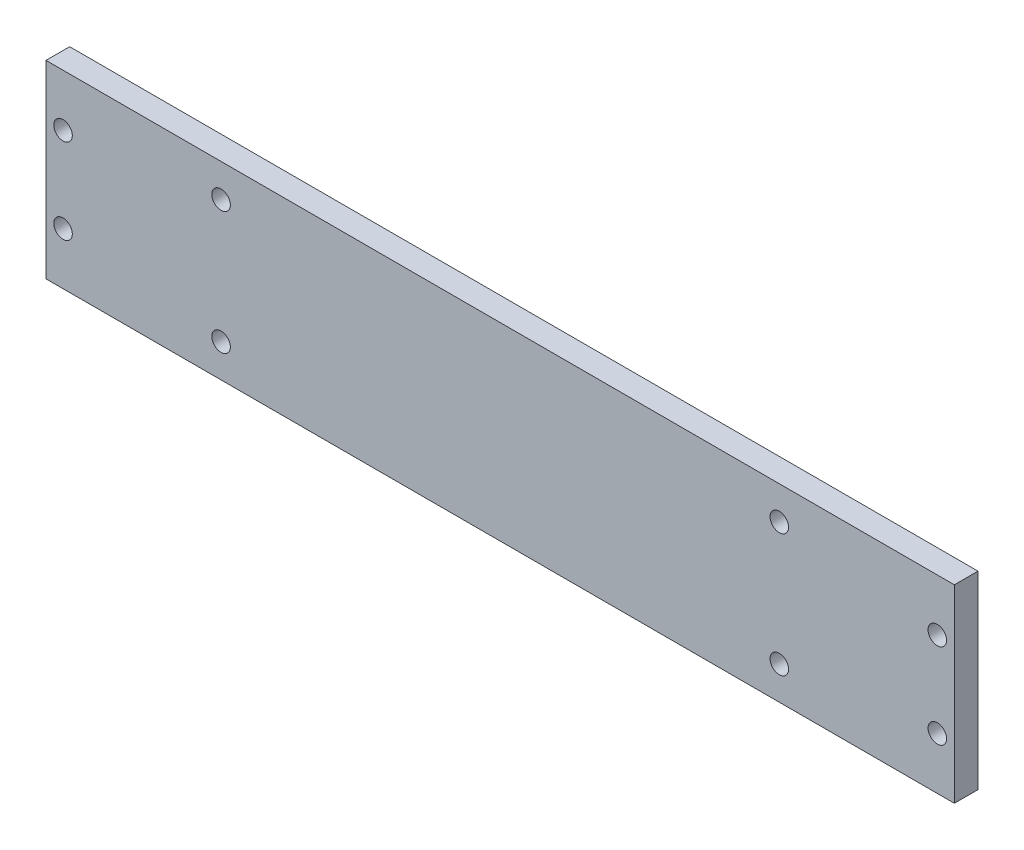
SolidWorks part; units mm, degrees
material "6061-T6 (SS)"
ref_plane "Front Plane" through (0, 0, 0) normal (0, 0, 1) x (1, 0, 0)
ref_plane "Top Plane" through (0, 0, 0) normal (0, 1, 0) x (1, 0, 0)
ref_plane "Right Plane" through (0, 0, 0) normal (1, 0, 0) x (0, 0, -1)
sketch "Sketch1" plane through (0, 0, 0) normal (0, 0, 1) x (1, 0, 0)
  line L1 (-121.92, 25.4) -> (121.92, 25.4)
  line L2 (-121.92, 25.4) -> (-121.92, -25.4)
  line L3 (-121.92, -25.4) -> (121.92, -25.4)
  line L4 (121.92, 25.4) -> (121.92, -25.4)
  line L5 (-121.92, 25.4) -> (121.92, -25.4) construction
  line L6 (-121.92, -25.4) -> (121.92, 25.4) construction
  point P0 (0, 0)
  dimension "D1" = 50.8
  dimension "D2" = 243.84
extrude "Boss-Extrude1" add sketch "Sketch1" along normal blind 6.35
sketch "Sketch2" plane through (0, 0, 6.35) normal (0, 0, 1) x (1, 0, 0)
  line L0 (121.92, -25.4) -> (121.92, 25.4) construction
  line L1 (-74.93, 16.51) -> (74.93, 16.51) construction
  line L2 (-74.93, 16.51) -> (-74.93, -16.51) construction
  line L3 (-74.93, -16.51) -> (74.93, -16.51) construction
  line L4 (74.93, 16.51) -> (74.93, -16.51) construction
  line L5 (-74.93, 16.51) -> (74.93, -16.51) construction
  line L6 (-74.93, -16.51) -> (74.93, 16.51) construction
  line L7 (117.348, -11.43) -> (-117.348, -11.43) construction
  line L8 (117.348, -11.43) -> (117.348, 11.43) construction
  line L9 (117.348, 11.43) -> (-117.348, 11.43) construction
  line L10 (-117.348, -11.43) -> (-117.348, 11.43) construction
  line L11 (117.348, -11.43) -> (-117.348, 11.43) construction
  line L12 (117.348, 11.43) -> (-117.348, -11.43) construction
  point P0 (0, 0)
  point P6 (0, 0)
  dimension "D1" = 149.86
  dimension "D2" = 33.02
  dimension "D3" = 4.572
  dimension "D4" = 22.86
hole_wizard "#10 Clearance Hole1" positions "Sketch3" profile "Sketch4" hole size "#10" standard "ANSI Inch" end condition through all
sketch "Sketch3" plane through (0, 0, 6.35) normal (0, 0, 1) x (1, 0, 0)
  point P0 (-74.93, 16.51)
  point P3 (-74.93, -16.51)
  point P6 (74.93, 16.51)
  point P9 (74.93, -16.51)
  point P12 (-117.348, 11.43)
  point P15 (-117.348, -11.43)
  point P18 (117.348, 11.43)
  point P21 (117.348, -11.43)
sketch "Sketch4" plane through (-74.93, 16.51, 6.35) normal (1, 0, 0) x (0, -1, 0)
  line L0 (0, 0) -> (0, 6.35)
  line L1 (0, 6.35) -> (2.4892, 6.35)
  line L2 (2.4892, 6.35) -> (2.4892, 0)
  line L5 (2.4892, 0) -> (0, 0)
  line L11 (0, -6.35) -> (0, 107.95) construction
  dimension "Thru Hole Dia." = 4.9784
  dimension "Thru Hole Depth" = 6.35
